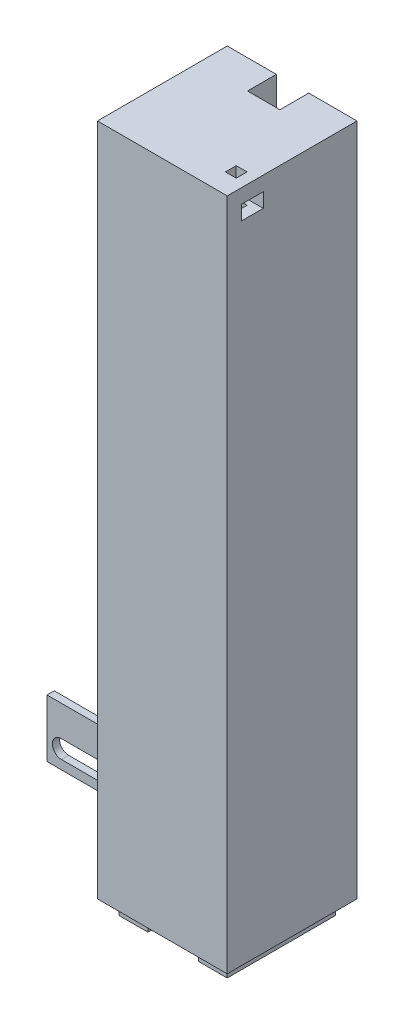
SolidWorks part; units mm, degrees
ref_plane "Front Plane" through (0, 0, 0) normal (0, 0, 1) x (1, 0, 0)
ref_plane "Top Plane" through (0, 0, 0) normal (0, 1, 0) x (1, 0, 0)
ref_plane "Right Plane" through (0, 0, 0) normal (1, 0, 0) x (0, 0, -1)
sketch "Sketch1" plane through (0, 0, 0) normal (0, 1, 0) x (1, 0, 0)
  line L1 (0, 0) -> (36, 0)
  line L2 (0, 0) -> (0, 36)
  line L3 (0, 36) -> (36, 36)
  line L4 (36, 0) -> (36, 36)
  dimension "D1" = 36
  dimension "D2" = 36
extrude "Boss-Extrude1" add sketch "Sketch1" along normal blind 186.9
sketch "Sketch2" plane through (0, 0, 0) normal (0, -1, 0) x (1, 0, 0)
  line L0 (0, 0) -> (36, 0) construction
  line L1 (3, -3) -> (7, -3)
  line L2 (3, -3) -> (3, -33)
  line L3 (3, -33) -> (7, -33)
  line L4 (7, -11) -> (7, -25)
  line L5 (36, -36) -> (0, -36) construction
  line L6 (0, -36) -> (0, 0) construction
  line L20 (36, 0) -> (36, -36) construction
  line L29 (7, -3) -> (11, -3)
  line L31 (7, -11) -> (11, -11)
  line L32 (11, -3) -> (11, -11)
  line L33 (7, -25) -> (11, -25)
  line L35 (7, -33) -> (11, -33)
  line L36 (11, -25) -> (11, -33)
  line L45 (29, -3) -> (33, -3)
  line L46 (29, -11) -> (29, -25)
  line L47 (29, -33) -> (33, -33)
  line L48 (33, -3) -> (33, -33)
  line L50 (29, -3) -> (25, -3)
  line L52 (29, -11) -> (25, -11)
  line L53 (25, -3) -> (25, -11)
  line L54 (29, -33) -> (25, -33)
  line L56 (29, -25) -> (25, -25)
  line L57 (25, -33) -> (25, -25)
  dimension "D1" = 3
  dimension "D2" = 3
  dimension "D3" = 3
  dimension "D4" = 4
  dimension "D5" = 4
  dimension "D6" = 8
  dimension "D7" = 8
  dimension "D8" = 4
  dimension "D9" = 3
  dimension "D10" = 3
  dimension "D11" = 3
  dimension "D12" = 4
  dimension "D13" = 4
  dimension "D14" = 4
extrude "Boss-Extrude2" add sketch "Sketch2" along normal blind 4
sketch "Sketch3" plane through (0, 0, 0) normal (0, -1, 0) x (1, 0, 0)
  line L0 (36, -36) -> (0, -36) construction
  line L2 (0, -36) -> (0, 0) construction
  circle A0 centre (18, -18) radius 2
  dimension "D1" = 4
  dimension "D2" = 18
  dimension "D3" = 18
extrude "Cut-Extrude1" cut sketch "Sketch3" against normal blind 5
sketch "Sketch4" plane through (0, 0, -36) normal (0, 0, 1) x (1, 0, 0)
  line L0 (0, 186.9) -> (36, 186.9) construction
  line L1 (13.62, 186.9) -> (22.62, 186.9)
  line L2 (13.62, 186.9) -> (13.62, 0)
  line L3 (13.62, 0) -> (22.62, 0)
  line L4 (22.62, 186.9) -> (22.62, 0)
  line L5 (0, 0) -> (36, 0) construction
  line L7 (36, 186.9) -> (36, 0) construction
  dimension "D1" = 13.38
  dimension "D2" = 9
extrude "Cut-Extrude2" cut sketch "Sketch4" along normal blind 8
sketch "Sketch5" plane through (36, 0, 0) normal (1, 0, 0) x (0, 0, -1)
  line L0 (0, 186.9) -> (36, 186.9) construction
  line L1 (4, 182.9) -> (10, 182.9)
  line L2 (4, 182.9) -> (4, 178.9)
  line L3 (4, 178.9) -> (10, 178.9)
  line L4 (10, 182.9) -> (10, 178.9)
  line L5 (0, 186.9) -> (0, 0) construction
  dimension "D1" = 6
  dimension "D2" = 4
  dimension "D3" = 4
  dimension "D4" = 4
extrude "Cut-Extrude3" cut sketch "Sketch5" against normal blind 9
sketch "Sketch6" plane through (0, 186.9, 0) normal (0, 1, 0) x (1, 0, 0)
  line L0 (36, 0) -> (36, 36) construction
  line L1 (30, 8.5) -> (33, 8.5)
  line L2 (30, 8.5) -> (30, 5.5)
  line L3 (30, 5.5) -> (33, 5.5)
  line L4 (33, 8.5) -> (33, 5.5)
  line L5 (0, 0) -> (36, 0) construction
  dimension "D1" = 3
  dimension "D2" = 3
  dimension "D3" = 3
  dimension "D4" = 5.5
extrude "Cut-Extrude4" cut sketch "Sketch6" against normal blind 10
sketch "Sketch7" plane through (0, 0, 0) normal (-1, 0, 0) x (0, 0, 1)
  line L0 (-36, 186.9) -> (-36, 0) construction
  line L1 (-28, 0) -> (-26, 0)
  line L2 (-28, 0) -> (-28, 16)
  line L3 (-28, 16) -> (-26, 16)
  line L4 (-26, 0) -> (-26, 16)
  point P5 (0, 0)
  dimension "D1" = 2
  dimension "D2" = 16
  dimension "D3" = 8
extrude "Boss-Extrude3" add sketch "Sketch7" along normal blind 40
sketch "Sketch8" plane through (0, 0, -26) normal (0, 0, 1) x (1, 0, 0)
  line L0 (-40, 0) -> (0, 0) construction
  line L1 (-40, 0) -> (-40, 16) construction
  line L3 (-36, 7.5) -> (-12, 7.5)
  line L5 (-36, 2.5) -> (-12, 2.5)
  arc A0 (-36, 7.5) -> (-36, 2.5) centre (-36, 5) ccw
  arc A1 (-12, 2.5) -> (-12, 7.5) centre (-12, 5) ccw
  dimension "D1" = 5
  dimension "D2" = 5
  dimension "D4" = 5
  dimension "D3" = 4
  dimension "D5" = 5
  dimension "D6" = 24
extrude "Cut-Extrude5" cut sketch "Sketch8" against normal up to next
